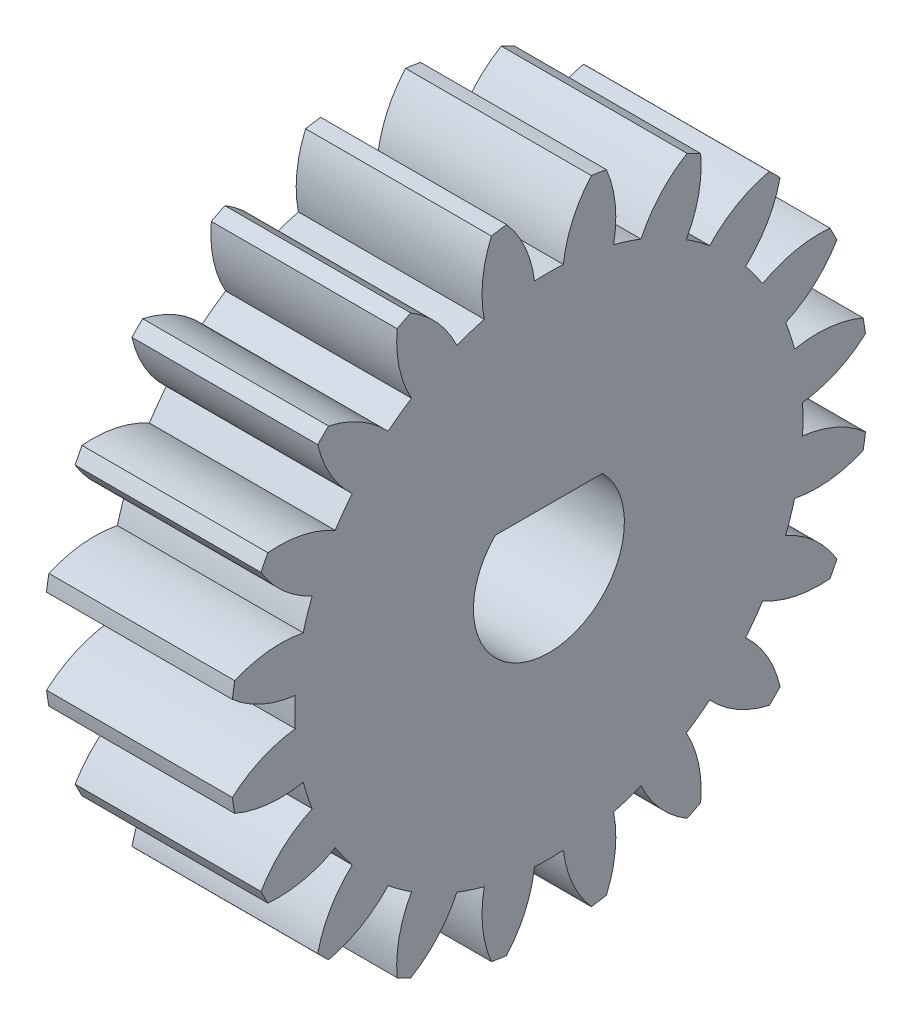
SolidWorks part; units mm, degrees
ref_plane "Plane1" through (0, 0, 0) normal (0, 0, 1) x (1, 0, 0)
ref_plane "Plane2" through (0, 0, 0) normal (0, 1, 0) x (1, 0, 0)
ref_plane "Plane3" through (0, 0, 0) normal (1, 0, 0) x (0, 0, -1)
sketch "HoldingSke" plane through (0, 0, 0) normal (0, 1, 0) x (1, 0, 0)
  line L0 (0, 0) -> (0.7518, -0.2736)
  line L1 (-15, 0) -> (100, 0) construction
  line L2 (0, 0) -> (-2.1039, 2.3779)
  line L3 (0, 0) -> (-11.863, 4.5341)
  line L4 (0, 0) -> (8.1152, 2.9537)
  line L5 (0, 0) -> (-46.8476, -17.4728)
  line L6 (0, 0) -> (-6.6317, -4.4744)
  line L7 (-2.1039, 2.3779) -> (8.6586, 51.2059)
  line L8 (-76.2, 54.61) -> (-75.2, 54.61)
  line L9 (-71.009, 38.7566) -> (-53.1078, 45.2721)
  line L10 (-76.2, 71.12) -> (104.1128, 71.12)
  line L11 (0, 0) -> (-8, 0)
  line L12 (-76.2, 101.6) -> (-76.155, 101.6)
  line L13 (24.9733, 27.94) -> (52.9518, 28.4284)
  line L14 (24.9733, 27.94) -> (24.9743, 27.94)
  line L15 (24.9733, 27.94) -> (100.4006, 29.5858)
  line L16 (-63.627, -1.25) -> (-12.827, -1.25)
  circle A0 centre (0, 0) radius 3.5
  circle A1 centre (0, 0) radius 10.9365
  circle A2 centre (0, 0) radius 37.5
  circle A3 centre (0, 0) radius 3.5
  dimension "Num_teeth" = 20
  dimension "Pitch_radius" = 180.3128
  dimension "Width" = 8
  dimension "Thickness" = 8
sketch "BasProSke" plane through (0, 0, 0) normal (0, 1, 0) x (1, 0, 0)
  line L0 (-10, 0) -> (60, 0) construction
  line L1 (0, 0) -> (0, 13.75)
  line L2 (0, 0) -> (8, 0)
  line L3 (8, 0) -> (8, 13.75)
  line L4 (8, 13.75) -> (0, 13.75)
  dimension "Thickness" = 8
  dimension "Diameter" = 27.5
revolve "Base-Revolve" add sketch "BasProSke" angle 360 about L0
sketch "TooCutSke" plane through (0, 0, 0) normal (1, 0, 0) x (0, 0, -1)
  line L1 (0, 0) -> (0, 107) construction
  line L2 (0, 0) -> (-1.0594, 12.455) construction
  line L3 (0, 0) -> (-3.9007, 24.6278) construction
  line L4 (-1.0594, 12.455) -> (-1.9503, 12.3139) construction
  arc A0 (0.6211, 10.9188) -> (-0.6211, 10.9188) centre (0, 0) ccw
  arc A1 (1.8466, 13.6511) -> (-1.8466, 13.6511) centre (0, 0) ccw
  circle A2 centre (0, 0) radius 12.5 construction
  circle A3 centre (0, 0) radius 11.7462 construction
  arc A4 (-0.6211, 10.9188) -> (-1.8466, 13.6511) centre (-5.5866, 10.3326) ccw
  arc A5 (1.8466, 13.6511) -> (0.6211, 10.9188) centre (5.5866, 10.3326) ccw
extrude "ToothCut" cut sketch "TooCutSke" along normal through all
fillet "Breaks" [suppressed] radius 0.025 tangent propagation no
fillet "RootFillets" [suppressed] radius 0.3135
pattern_circular "TeethCuts" count 20 every 18 about axis through (-10, 0, 0) along (1, 0, 0) of "ToothCut", "RootFillets", "Breaks"
sketch "HubNeaOneSke" plane through (0, 0, 0) normal (-1, 0, 0) x (0, 0, 1)
  circle A0 centre (0, 0) radius 10.9365
  dimension "Diameter" = 21.873
extrude "HubNearOne" [suppressed] add sketch "HubNeaOneSke" along normal blind 42.0001
sketch "HubNeaBotSke" plane through (0, 0, 0) normal (-1, 0, 0) x (0, 0, 1)
  circle A0 centre (0, 0) radius 10.9365
  dimension "Diameter" = 21.873
extrude "HubNearBoth" [suppressed] add sketch "HubNeaBotSke" along normal blind 21
ref_plane "FarPln" through (8, 0, 0) normal (1, 0, 0) x (0, 0, -1)
sketch "HubFarSke" plane through (8, 0, 0) normal (1, 0, 0) x (0, 0, -1)
  circle A0 centre (0, 0) radius 10.9365
  dimension "Diameter" = 21.873
extrude "HubFar" [suppressed] add sketch "HubFarSke" along normal blind 21
sketch "BorSke" plane through (0, 0, 0) normal (1, 0, 0) x (0, 0, -1)
  circle A0 centre (0, 0) radius 3.5
  dimension "Diameter" = 7
extrude "Bore" cut sketch "BorSke" along normal mid plane 100.0001
sketch "KeySke" plane through (0, 0, 0) normal (1, 0, 0) x (0, 0, -1)
  line L0 (-1, 0) -> (-1, 4.5)
  line L1 (-1, 4.5) -> (1, 4.5)
  line L2 (1, 4.5) -> (1, 0)
  line L3 (0, 0) -> (0, 34) construction
  line L4 (-1, 0) -> (1, 0)
  dimension "Width" = 2
extrude "Keyway" [suppressed] cut sketch "KeySke" along normal mid plane 100.0001
pattern_circular "Keyway2" [suppressed] count 2 every 90 about axis through (-10, 0, 0) along (1, 0, 0) reverse direction yes
sketch "Sketch1" plane through (8, 0, 0) normal (1, 0, 0) x (0, 0, -1)
  line L0 (-2.65, 2.2864) -> (2.65, 2.2864)
  circle A0 centre (0, 0) radius 3.5 construction
  circle A1 centre (0, 0) radius 3.5
  circle A2 centre (0, 0) radius 3.25
  dimension "D2" = 6.5
  dimension "D1" = 5.3
extrude "Boss-Extrude3" add sketch "Sketch1" against normal up to surface (8 mm away) contours A2 L0 A1 | A2 L0 A1 | L0 A2 region at (8, 3.4456, 0) region at (8, 2.1956, 2.4799) region at (8, 2.6772, 0) up to face at (0, 0, -3.5)
equation "' \"Module@HoldingSke\" = 6.35"
equation "' \"Num_teeth@HoldingSke\" = 12"
equation "' \"Ap@HoldingSke\" =  20"
equation "' \"Ap@HoldingSke\" = 20"
equation "' \"Width@HoldingSke\" = 0.5 * 25.4"
equation "' \"Hub_dia@HoldingSke\"= 1 * 25.4"
equation "' \"Hub_dia@HoldingSke\" = 1 * 25.4"
equation "' \"Overall_len@HoldingSke\" = 1.0 * 25.4"
equation "' \"Bore@HoldingSke\" = 0.75 * 25.4"
equation "' \"T_dim@HoldingSke\" = 0.1 * 25.4"
equation "' \"Width@KeySke\" = 0.25 * 25.4"
equation "' \"Show_teeth@HoldingSke\" = 13"
equation "' \"Backlash@HoldingSke\" = 0.009 * 25.4"
equation "' \"Addendum_fac@HoldingSke\" = 1.0"
equation "' \"Dedendum_fac@HoldingSke\" = 1.25"
equation "' \"Dedendum_add@HoldingSke\" = 0.00005 * 25.4"
equation "' \"Clearance_fac@HoldingSke\" = 0.25"
equation "\"Pitch@HoldingSke\" = 1 / \"Module@HoldingSke\""
equation "\"Overcut_dia@TooCutSke\" = (\"Num_teeth@HoldingSke\" + 2 * \"Addendum_fac@HoldingSke\") / \"Pitch@HoldingSke\" + 0.002 * 25.4"
equation "\"Pitch_dia@TooCutSke\" = \"Num_teeth@HoldingSke\" / \"Pitch@HoldingSke\""
equation "\"Base_dia@TooCutSke\" = \"Num_teeth@HoldingSke\" / \"Pitch@HoldingSke\" * cos((\"Ap@HoldingSke\"  * 3.14159265 / 180))"
equation "\"Root_dia@TooCutSke\" = (\"Num_teeth@HoldingSke\" + 2) / \"Pitch@HoldingSke\" - 2 * (\"Addendum_fac@HoldingSke\" + \"Dedendum_fac@HoldingSke\") / \"Pitch@HoldingSke\" - \"Dedendum_add@HoldingSke\" * 2"
equation "\"Half_ang@TooCutSke\" = 180 / \"Num_teeth@HoldingSke\""
equation "\"Half_CT@TooCutSke\" = \"Num_teeth@HoldingSke\" / \"Pitch@HoldingSke\" * sin((3.14159265 / 2 / \"Num_teeth@HoldingSke\")) / 2 - 7 * \"Backlash@HoldingSke\" / 4"
equation "\"Flank_rad@TooCutSke\" = \"Num_teeth@HoldingSke\" / \"Pitch@HoldingSke\" / 5"
equation "\"Radius@RootFillets\" = \"Clearance_fac@HoldingSke\" / \"Pitch@HoldingSke\" + \"Dedendum_add@HoldingSke\""
equation "\"Break_rad@Breaks\" = 0.02 / \"Pitch@HoldingSke\""
equation "\"Thickness@HoldingSke\" = \"Width@HoldingSke\""
equation "\"OAL@HoldingSke\" = \"Thickness@HoldingSke\""
equation "\"MHD@HoldingSke\" = (\"Num_teeth@HoldingSke\" + 2) / \"Pitch@HoldingSke\" - 2 * (\"Addendum_fac@HoldingSke\" + \"Dedendum_fac@HoldingSke\")  / \"Pitch@HoldingSke\" - \"Dedendum_add@HoldingSke\" * 2"
equation "\"MBD@HoldingSke\" = (\"Num_teeth@HoldingSke\" + 2) / \"Pitch@HoldingSke\" - 2 * (\"Addendum_fac@HoldingSke\" + \"Dedendum_fac@HoldingSke\")  / \"Pitch@HoldingSke\" - \"Dedendum_add@HoldingSke\" * 2 - 0.002 * 25.4"
equation "\"MHD@HoldingSke\" = ((sgn( \"MHD@HoldingSke\" - \"Hub_dia@HoldingSke\" )-1)*( \"MHD@HoldingSke\" - \"Hub_dia@HoldingSke\" ))/-2+ \"Hub_dia@HoldingSke\""
equation "\"MBD@HoldingSke\" = ((sgn( \"MBD@HoldingSke\" - \"Bore@HoldingSke\" )-1)*( \"MBD@HoldingSke\" - \"Bore@HoldingSke\" ))/-2+ \"Bore@HoldingSke\""
equation "\"OAL@HoldingSke\" = ((sgn( \"OAL@HoldingSke\" - \"Overall_len@HoldingSke\" )+1)*( \"OAL@HoldingSke\" - \"Overall_len@HoldingSke\" ))/2 + \"Overall_len@HoldingSke\" + 0.000002 * 25.4"
equation "\"Num_teeth@TeethCuts\" = int( \"Show_teeth@HoldingSke\" ) + 1"
equation "\"Num_teeth@TeethCuts\" = ((sgn( \"Num_teeth@TeethCuts\" - \"Num_teeth@HoldingSke\" )-1)*( \"Num_teeth@TeethCuts\" - \"Num_teeth@HoldingSke\" ))/-2+ \"Num_teeth@HoldingSke\""
equation "\"Num_teeth@TeethCuts\" = ((sgn( \"Num_teeth@TeethCuts\" - 2.0)+1)*( \"Num_teeth@TeethCuts\" - 2.0))/2 +2.0"
equation "\"Angle@TeethCuts\" = 360.0 / \"Num_teeth@HoldingSke\""
equation "\"Diameter@BasProSke\" = (\"Num_teeth@HoldingSke\" + 2 * \"Addendum_fac@HoldingSke\") / \"Pitch@HoldingSke\""
equation "\"Thickness@BasProSke\"  = \"Thickness@HoldingSke\""
equation "' \"Fillet_rad@BasProSke\" =  \"Thickness@HoldingSke\" * 0.05"
equation "' \"Fillet_rad@BasProSke\" = \"Thickness@HoldingSke\" * 0.05"
equation "\"MHD@HoldingSke\" = ((sgn( \"MHD@HoldingSke\" - \"Root_dia@TooCutSke\" )-1)*( \"MHD@HoldingSke\" - \"Root_dia@TooCutSke\" ))/-2+ \"Root_dia@TooCutSke\""
equation "\"Diameter@HubNeaOneSke\" = \"MHD@HoldingSke\""
equation "\"Length@HubNearOne\" = \"OAL@HoldingSke\" - \"Thickness@BasProSke\""
equation "\"Diameter@HubNeaBotSke\" = \"MHD@HoldingSke\""
equation "\"Length@HubNearBoth\" = ( \"OAL@HoldingSke\" - \"Thickness@BasProSke\" ) / 2.0"
equation "\"Thickness@FarPln\" = \"Thickness@BasProSke\""
equation "\"Diameter@HubFarSke\" = \"MHD@HoldingSke\""
equation "\"Length@HubFar\" = ( \"OAL@HoldingSke\" - \"Thickness@BasProSke\" ) / 2.0"
equation "\"Diameter@BorSke\" = \"MBD@HoldingSke\""
equation "\"D1@Bore\" = \"OAL@HoldingSke\" * 2.0"
equation "\"D1@Keyway\" = \"OAL@HoldingSke\" * 2.0"
equation "\"Offset@KeySke\" = \"T_dim@HoldingSke\" + \"MBD@HoldingSke\" / 2.0"
